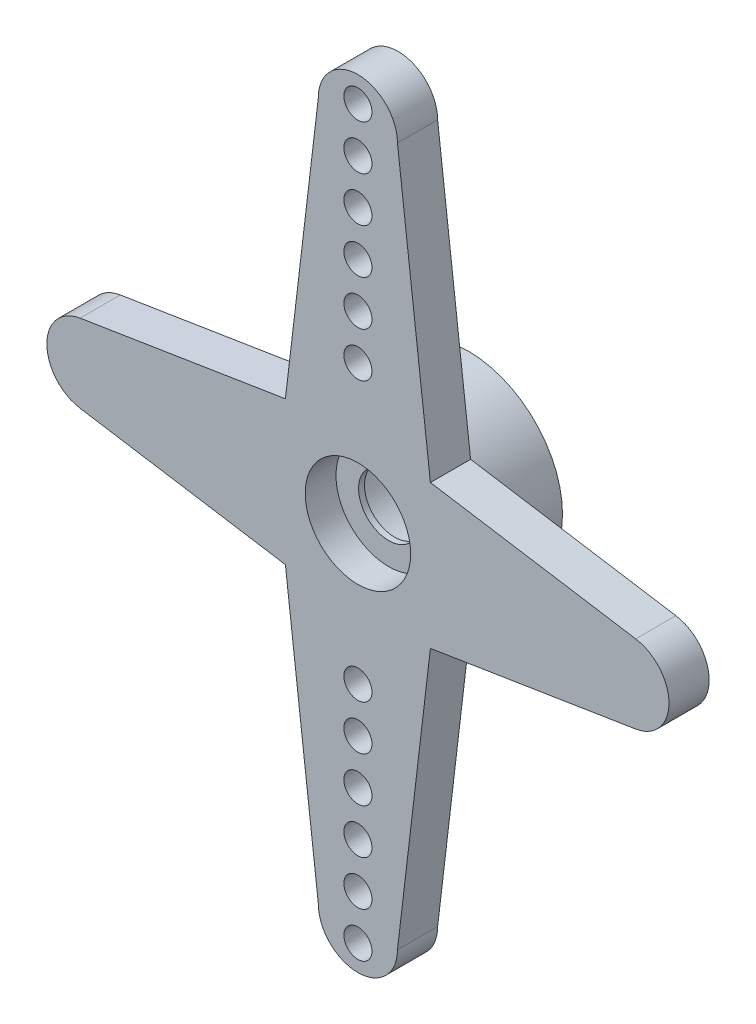
SolidWorks part; units mm, degrees
material "Nylon 6/10"
ref_plane "Front Plane" through (0, 0, 0) normal (0, 0, 1) x (1, 0, 0)
ref_plane "Top Plane" through (0, 0, 0) normal (0, 1, 0) x (1, 0, 0)
ref_plane "Right Plane" through (0, 0, 0) normal (1, 0, 0) x (0, 0, -1)
ref_plane "Plane1" through (0, 0, -7.033) normal (0, 0, 1) x (1, 0, 0)
sketch "Sketch1" plane through (0, 0, -7.033) normal (0, 0, 1) x (1, 0, 0)
  circle A0 centre (-5.5, 0) radius 3.5687
  circle A1 centre (-5.5, 0) radius 2
  dimension "D1" = 7.1374
extrude "Boss-Extrude1" add sketch "Sketch1" along normal blind 4.191
sketch "Sketch5" plane through (0, 0, -4.233) normal (0, 0, 1) x (1, 0, 0)
  circle A0 centre (-5.5, 0) radius 1.143
  circle A1 centre (-5.5, 0) radius 2 construction
  circle A2 centre (-5.5, 0) radius 2
  dimension "D1" = 2.286
extrude "Boss-Extrude2" add sketch "Sketch5" along normal offset from surface (0.2226 mm away) 1.1684 up to face at (-1.9313, 0, -2.842)
sketch "Sketch6" plane through (0, 0, -2.842) normal (0, 0, 1) x (1, 0, 0)
  line L0 (-4, -13.25) -> (-2.6869, -2.196)
  line L1 (-7, -13.25) -> (-8.313, -2.196)
  line L2 (-5.5, 0) -> (-5.5, -13.25) construction
  line L3 (-5.5, -13.7834) -> (-5.5, -12.0816) construction
  arc A0 (-7, -13.25) -> (-4, -13.25) centre (-5.5, -13.25) ccw
  circle A1 centre (-5.5, 0) radius 3.5687 construction
  circle A2 centre (-5.5, 0) radius 3.5687 construction
  circle A3 centre (-5.5, -12.0816) radius 0.5334
  circle A4 centre (-5.5, -13.7834) radius 0.5334
  circle A5 centre (-5.5, -10.3798) radius 0.5334
  circle A6 centre (-5.5, -8.678) radius 0.5334
  circle A7 centre (-5.5, -6.9762) radius 0.5334
  circle A8 centre (-5.5, -5.2744) radius 0.5334
  arc A9 (-2.6869, -2.196) -> (-8.313, -2.196) centre (-5.5, 0) cw
  dimension "D1" = 3
  dimension "D2" = 14.75
  dimension "D4" = 1.0668
  dimension "D3" = 5.6261
  dimension "D6" = 1.7018
  dimension "D5" = 6
extrude "Boss-Extrude3" add sketch "Sketch6" against normal blind 1.524
mirror "Mirror1" about plane through (0, 0, 0) normal (0, 1, 0) of "Boss-Extrude3"
sketch "Sketch7" plane through (0, 0, -2.842) normal (0, 0, 1) x (1, 0, 0)
  line L0 (-16.0365, -1.4812) -> (-7.696, -2.8131)
  line L1 (-16.0365, 1.4812) -> (-7.696, 2.8131)
  line L2 (-5.5, 0) -> (-15.8, 0) construction
  line L3 (-7.696, 2.8131) -> (-7.696, -2.8131) construction
  arc A0 (-16.0365, 1.4812) -> (-16.0365, -1.4812) centre (-15.8, 0) ccw
  circle A1 centre (-5.5, 0) radius 3.5687 construction
  arc A8 (-7.696, -2.8131) -> (-7.696, 2.8131) centre (-5.5, 0) cw
  arc A9 (-2.6869, -2.196) -> (-2.6869, 2.196) centre (-5.5, 0) ccw construction
  dimension "D1" = 3
  dimension "D2" = 11.8
  dimension "D3" = 5.6261
extrude "Boss-Extrude4" add sketch "Sketch7" against normal up to surface (1.524 mm away) up to face at (-5.5, 8.4412, -4.366)
ref_plane "Plane2" through (-1.9313, 0, 0) normal (1, 0, 0) x (0, 0, -1)
ref_plane "Plane3" through (-9.0687, 0, 0) normal (-1, 0, 0) x (0, 0, 1)
ref_plane "Plane4" through (-5.5, 0, 0) normal (-1, 0, 0) x (0, 0, 1)
mirror "Mirror2" about plane through (-5.5, 0, 0) normal (-1, 0, 0) of "Boss-Extrude4"
